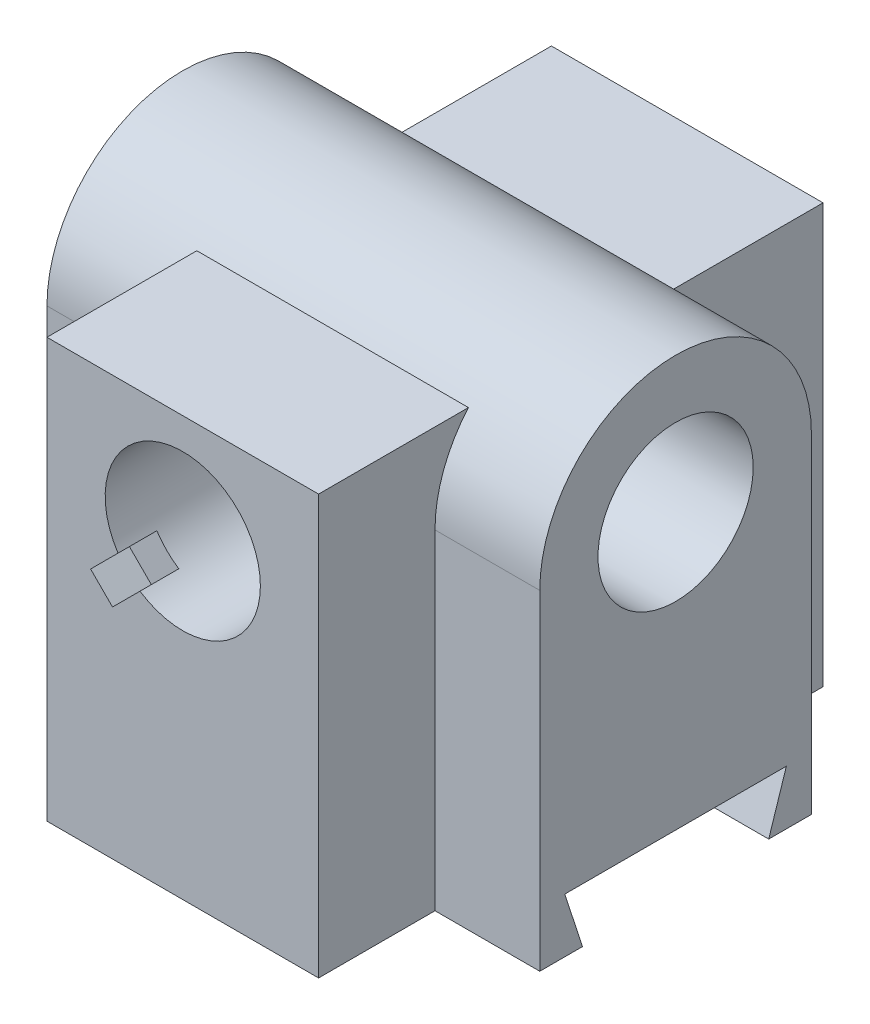
SolidWorks part; units mm, degrees
ref_plane "Front Plane" through (0, 0, 0) normal (0, 0, 1) x (1, 0, 0)
ref_plane "Top Plane" through (0, 0, 0) normal (0, 1, 0) x (1, 0, 0)
ref_plane "Right Plane" through (0, 0, 0) normal (1, 0, 0) x (0, 0, -1)
sketch "Sketch1" plane through (0, 0, 0) normal (1, 0, 0) x (0, 0, -1)
  line L1 (-17.5, 30) -> (17.5, 30)
  line L2 (-17.5, 30) -> (-17.5, -30)
  line L3 (-17.5, -30) -> (17.5, -30)
  line L4 (17.5, 30) -> (17.5, -30)
  dimension "D1" = 35
  dimension "D2" = 60
  dimension "D3" = 17.5
  dimension "D4" = 30
extrude "Boss-Extrude1" add sketch "Sketch1" along normal blind 31 and the other way blind 32.5
fillet "Fillet2" 2 edges at (-0.75, 30, 17.5) (-0.75, 30, -17.5) type full round first side face at (-0.75, 0, 17.5) second side face at (-0.75, 0, -17.5) middle face at (-0.75, 30, 0)
sketch "Sketch8" plane through (0, 0, 0) normal (0, 0, 1) x (1, 0, 0)
  line L0 (-32.5, -30) -> (31, -30) construction
  line L1 (-17.5, 24) -> (17.5, 24)
  line L2 (-17.5, 24) -> (-17.5, -30)
  line L3 (-17.5, -30) -> (17.5, -30)
  line L4 (17.5, 24) -> (17.5, -30)
  dimension "D1" = 17.5
  dimension "D2" = 35
  dimension "D3" = 54
extrude "Boss-Extrude2" add sketch "Sketch8" along normal blind 32.5 and the other way blind 32.5 contours L1 L4 L3 L2
hole_wizard "Hole2" positions "Sketch12" profile "Sketch13" legacy end condition through all
sketch "Sketch12" plane through (0, 0, 32.5) normal (0, 0, 1) x (1, 0, 0)
  line L0 (-17.5, -30) -> (17.5, -30) construction
  line L1 (17.5, 24) -> (17.5, -30) construction
  point P0 (0, 10)
  dimension "D1" = 40
  dimension "D2" = 17.5
sketch "Sketch13" plane through (0, 10, 32.5) normal (1, 0, 0) x (0, -1, 0)
  line L0 (0, 0) -> (0, 65)
  line L1 (0, 65) -> (10, 65)
  line L2 (10, 65) -> (10, 0)
  line L3 (10, 0) -> (0, 0)
  line L4 (0, 110) -> (0, -10) construction
  dimension "Diameter" = 20
  dimension "Depth" = 65
sketch "Sketch14" plane through (0, 0, 32.5) normal (0, 0, 1) x (1, 0, 0)
  line L0 (0, 10) -> (-14.8858, -4.8858) construction
  line L1 (0, 10) -> (0, -12.9865) construction
  line L2 (-8.3424, 4.486) -> (-11.878, 0.9505)
  line L3 (-11.878, 0.9505) -> (-9.0495, -1.878)
  line L4 (-9.0495, -1.878) -> (-5.514, 1.6576)
  circle A0 centre (0, 10) radius 10 construction
  arc A1 (-8.3424, 4.486) -> (-5.514, 1.6576) centre (0, 10) ccw
  point P2 (-6.77, -3.3097)
  dimension "D2" = 5
  dimension "D1" = 4
  dimension "D3" = 45
extrude "Cut-Extrude1" cut sketch "Sketch14" against normal blind 5
sketch "Sketch15" plane through (31, 0, 0) normal (1, 0, 0) x (0, 0, -1)
  line L0 (0, 0) -> (0, -34.57) construction
  line L1 (-12, -30) -> (-14.2744, -23)
  line L2 (-17.5, -30) -> (17.5, -30) construction
  line L3 (-14.2744, -23) -> (14.2744, -23)
  line L4 (14.2744, -23) -> (12, -30)
  line L5 (12, -30) -> (-12, -30)
  dimension "D1" = 24
  dimension "D2" = 7
  dimension "D3" = 72
extrude "Cut-Extrude2" cut sketch "Sketch15" against normal through all
hole_wizard "Hole3" positions "Sketch16" profile "Sketch17" legacy end condition through all
sketch "Sketch16" plane through (31, 0, 0) normal (1, 0, 0) x (0, 0, -1)
  point P0 (0, 12.5)
sketch "Sketch17" plane through (31, 12.5, 0) normal (0, 1, 0) x (0, 0, -1)
  line L0 (0, 0) -> (0, 63.5)
  line L1 (0, 63.5) -> (10, 63.5)
  line L2 (10, 63.5) -> (10, 0)
  line L3 (10, 0) -> (0, 0)
  line L4 (0, 110) -> (0, -10) construction
  dimension "Diameter" = 20
  dimension "Depth" = 63.5
